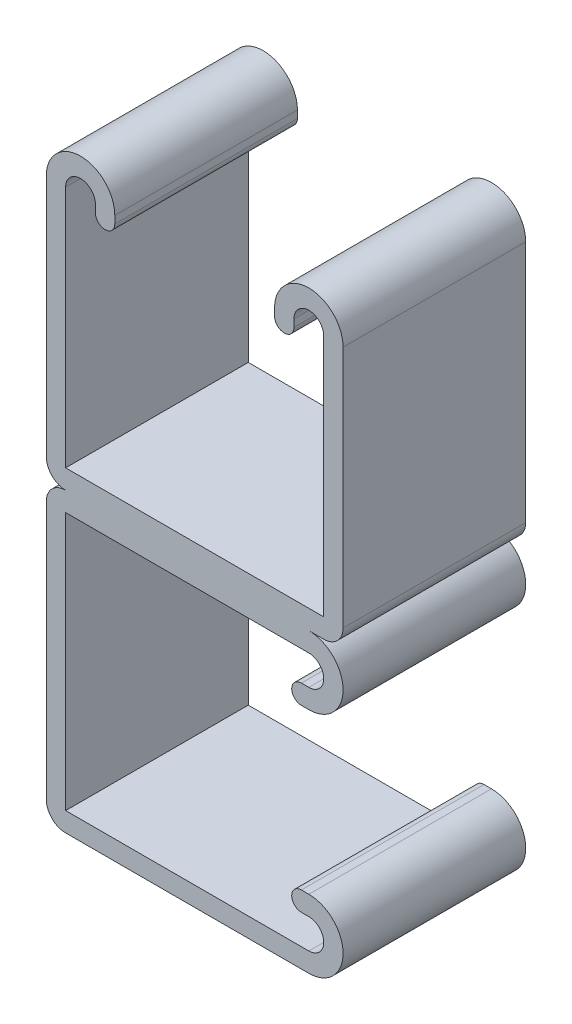
SolidWorks part; units mm, degrees
note: '?' marks a value the reader was unsure of.
ref_plane "Plane1" through (0, 0, 0) normal (0, 0, 1) x (1, 0, 0)
ref_plane "Plane2" through (0, 0, 0) normal (0, 1, 0) x (1, 0, 0)
ref_plane "Plane3" through (0, 0, 0) normal (1, 0, 0) x (0, 0, -1)
sketch "Sketch1" plane through (0, 0, 0) normal (0, 0, 1) x (1, 0, 0)
  line L0 (0, 36.5125) -> (0, 2.6924)
  line L1 (2.6924, 0) -> (38.5826, 0)
  line L2 (41.275, 2.6924) -> (41.275, 36.5125)
  line L3 (31.75, 36.5125) -> (31.75, 35.4774)
  line L4 (9.525, 36.5125) -> (9.525, 35.4774)
  line L5 (6.8326, 36.5125) -> (6.8326, 35.4774)
  line L6 (2.6924, 36.5125) -> (2.6924, 2.6924)
  line L7 (2.6924, 2.6924) -> (38.5826, 2.6924)
  line L8 (38.5826, 2.6924) -> (38.5826, 36.5125)
  line L9 (34.4424, 36.5125) -> (34.4424, 35.4774)
  line L10 (-4.7625, 41.275) -> (46.0375, 41.275) construction
  line L11 (7.7851, 34.1313) -> (33.4899, 34.1313) construction
  arc A0 (41.275, 36.5125) -> (31.75, 36.5125) centre (36.5125, 36.5125) ccw
  arc A1 (0, 36.5125) -> (9.525, 36.5125) centre (4.7625, 36.5125) cw
  arc A2 (2.6924, 0) -> (0, 2.6924) centre (2.6924, 2.6924) cw
  arc A3 (38.5826, 0) -> (41.275, 2.6924) centre (38.5826, 2.6924) ccw
  arc A4 (2.6924, 36.5125) -> (6.8326, 36.5125) centre (4.7625, 36.5125) cw
  arc A5 (38.5826, 36.5125) -> (34.4424, 36.5125) centre (36.5125, 36.5125) ccw
  arc A6 (31.75, 35.4774) -> (34.4424, 35.4774) centre (33.0962, 35.4774) ccw
  arc A7 (9.525, 35.4774) -> (6.8326, 35.4774) centre (8.1788, 35.4774) cw
  dimension "D6" = 9.525
  dimension "D7" = 22.225
  dimension "D9" = 7.1437
  dimension "D2" = 41.275
extrude "Base-Extrude" add sketch "Sketch1" along normal mid plane 25.4
ref_axis "Axis1" through (0, 0, -50) along (0, 0, 1)?
pattern_circular "CirPattern1" count 2 every 270 about axis through (0, 0, 0) along (0, 0, 1) of "Base-Extrude"
equation "\"D7@Sketch1\" = \"Width@Sketch1\" - 2 * \"D6@Sketch1\""
equation "\"D1@Sketch1\" = \"gauge@Sketch1\""
